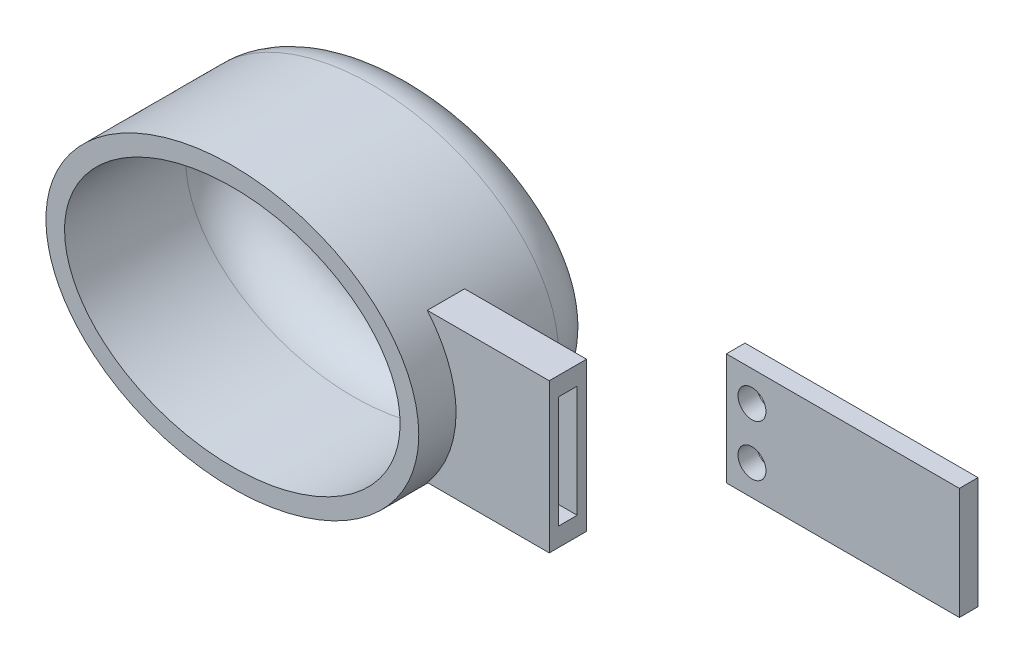
SolidWorks part; units mm, degrees
note: The reader was unsure of these and kept them because the rebuilt part matched: shared geometry of "Sketch3<3>".
ref_plane "Front Plane" through (0, 0, 0) normal (0, 0, 1) x (1, 0, 0)
ref_plane "Top Plane" through (0, 0, 0) normal (0, 1, 0) x (1, 0, 0)
ref_plane "Right Plane" through (0, 0, 0) normal (1, 0, 0) x (0, 0, -1)
sketch "Sketch1" plane through (0, 0, 0) normal (0, 0, 1) x (1, 0, 0)
  line L0 (0, 0) -> (20, 0) construction
  line L1 (20, 0) -> (4.5823, 0) construction
  ellipse E0 centre (0, 0) end of major axis (20, 0) minor radius 15
  dimension "D1" = 20
  dimension "D2" = 15
extrude "Boss-Extrude1" add sketch "Sketch1" along normal blind 20
shell "Shell1" thickness 2
fillet "Fillet3" radius 5 1 edges at (17.9338, 1.106, 2)
fillet "Fillet4" radius 5 1 edges at (20, 0, 0)
sketch "Sketch3" plane through (0, 0, 20) normal (0, 0, 1) x (1, 0, 0)
  line L0 (0, 0) -> (41.7937, 0) construction
  line L1 (30, 8) -> (30, -8)
  line L2 (30, -8) -> (16.9181, -8)
  line L3 (30, 8) -> (16.9181, 8)
  ellipse E0 centre (0, 0) end of major axis (20, 0) minor radius 15 construction
  ellipse E2 centre (0, 0) end of major axis (20, 0) minor radius 15
  ellipse E3 centre (0, 0) end of major axis (20, 0) minor radius 15 (16.9181, -8) -> (16.9181, 8) ccw
  dimension "D1" = 16
  dimension "D2" = 8
  dimension "D3" = 30
  dimension "D4" = 0
extrude "Boss-Extrude3" add sketch "Sketch3" against normal blind 8
extrude "Cut-Extrude2" cut sketch "Sketch3<3>" against normal blind 4
sketch "Sketch3<3>" plane through (0, 0, 20) normal (0, 0, 1) x (1, 0, 0) same geometry as "Sketch3"
sketch "Sketch12" plane through (30, 0, 0) normal (1, 0, 0) x (0, 0, -1)
  line L0 (-16, -8) -> (-16, 8) construction
  line L1 (-15, -6) -> (-13, -6)
  line L2 (-15, -6) -> (-15, 6)
  line L3 (-15, 6) -> (-13, 6)
  line L4 (-13, -6) -> (-13, 6)
  line L5 (-12, -8) -> (-16, -8) construction
  dimension "D1" = 12
  dimension "D2" = 2
  dimension "D3" = 1
  dimension "D4" = 2
extrude "Cut-Extrude3" cut sketch "Sketch12" against normal blind 8
sketch "Sketch13" plane through (0, 0, 0) normal (0, 0, 1) x (1, 0, 0)
  line L0 (0, 0) -> (75.4392, 0) construction
  line L1 (35, 6) -> (60, 6)
  line L2 (35, 6) -> (35, -6)
  line L3 (35, -6) -> (60, -6)
  line L4 (60, 6) -> (60, -6)
  dimension "D1" = 12
  dimension "D2" = 6
  dimension "D3" = 25
  dimension "D4" = 35
extrude "Boss-Extrude4" add sketch "Sketch13" along normal blind 2 separate body
sketch "Sketch15" plane through (0, 0, 2) normal (0, 0, 1) x (1, 0, 0)
  line L0 (60, 6) -> (35, 6) construction
  line L1 (35, -6) -> (60, -6) construction
  line L2 (35, 6) -> (35, -6) construction
  circle A0 centre (37.75, -2.75) radius 1.5
  circle A1 centre (37.75, 2.75) radius 1.5
  dimension "D1" = 3
  dimension "D2" = 3
  dimension "D3" = 3.25
  dimension "D4" = 3.25
  dimension "D5" = 2.75
  dimension "D6" = 2.75
extrude "Cut-Extrude4" cut sketch "Sketch15" against normal blind 10
